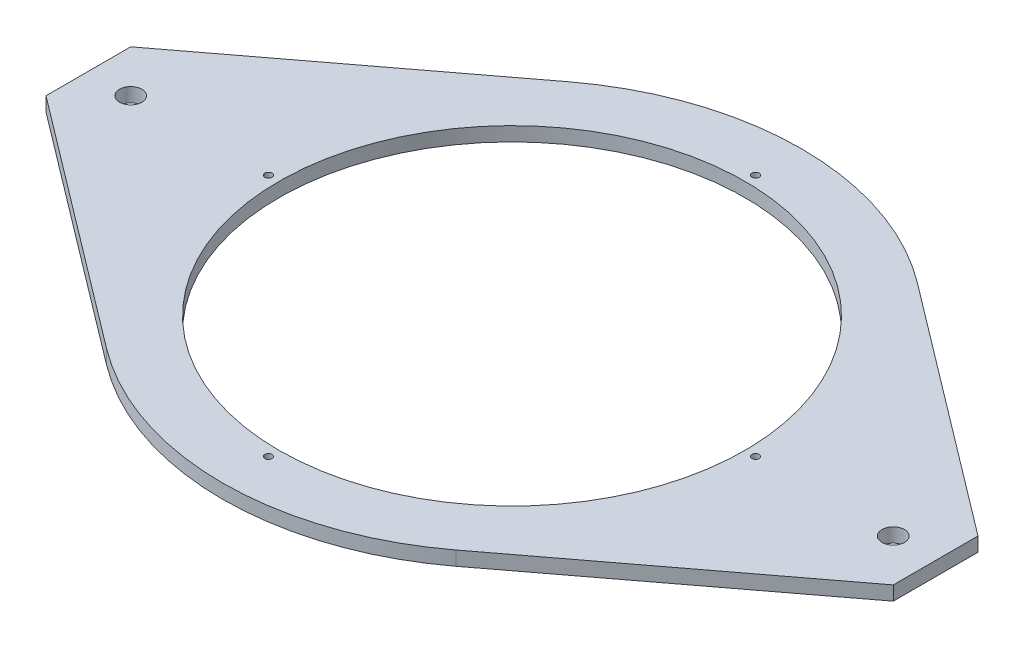
SolidWorks part; units mm, degrees
material "6061-T6 (SS)"
ref_plane "Front Plane" through (0, 0, 0) normal (0, 0, 1) x (1, 0, 0)
ref_plane "Top Plane" through (0, 0, 0) normal (0, 1, 0) x (1, 0, 0)
ref_plane "Right Plane" through (0, 0, 0) normal (1, 0, 0) x (0, 0, -1)
sketch "Sketch1" plane through (0, 0, 0) normal (0, 1, 0) x (1, 0, 0)
  line L2 (-190.5, 19.05) -> (-190.5, -19.05)
  line L4 (190.5, 19.05) -> (190.5, -19.05)
  line L5 (-190.5, 19.05) -> (190.5, -19.05) construction
  line L6 (-190.5, -19.05) -> (190.5, 19.05) construction
  line L8 (-190.5, 19.05) -> (-78.5743, 103.7864)
  line L9 (-190.5, -19.05) -> (-78.5743, -103.7864)
  line L10 (190.5, 19.05) -> (78.5743, 103.7864)
  line L11 (190.5, -19.05) -> (78.5743, -103.7864)
  circle A0 centre (0, 0) radius 104.775
  arc A1 (-78.5743, -103.7864) -> (78.5743, -103.7864) centre (0, 0) ccw
  arc A2 (78.5743, 103.7864) -> (-78.5743, 103.7864) centre (0, 0) ccw
  point P0 (0, 0)
  dimension "D3" = 209.55
  dimension "D4" = 25.4
  dimension "D1" = 381
  dimension "D2" = 38.1
extrude "Boss-Extrude1" add sketch "Sketch1" along normal blind 6.35
hole_wizard "#4 Clearance Hole1" positions "Sketch2" profile "Sketch3" hole size "#4" standard "ANSI Inch" end condition through all
sketch "Sketch2" plane through (0, 6.35, 0) normal (0, 1, 0) x (1, 0, 0)
  circle A0 centre (0, 0) radius 109.5375
  circle A1 centre (0, 0) radius 104.775 construction
  point P7 (0, 109.5375)
  point P9 (109.5375, 0)
  point P11 (0, -109.5375)
  point P13 (-109.5375, 0)
  dimension "D1" = 4.7625
sketch "Sketch3" plane through (0, 6.35, -109.5375) normal (1, 0, 0) x (0, 0, 1)
  line L0 (0, 0) -> (0, 6.35)
  line L1 (0, 6.35) -> (1.6319, 6.35)
  line L2 (1.6319, 6.35) -> (1.6319, 0)
  line L5 (1.6319, 0) -> (0, 0)
  line L11 (0, -6.35) -> (0, 107.95) construction
  dimension "Thru Hole Dia." = 3.2639
  dimension "Thru Hole Depth" = 6.35
hole_wizard "3/8 Clearance Hole1" positions "Sketch4" profile "Sketch5" hole size "3/8" standard "ANSI Inch" end condition through all
sketch "Sketch4" plane through (0, 6.35, 0) normal (0, 1, 0) x (1, 0, 0)
  line L0 (-171.45, 0) -> (171.45, 0) construction
  point P0 (-171.45, 0)
  point P2 (171.45, 0)
  dimension "D1" = 342.9
sketch "Sketch5" plane through (-171.45, 6.35, 0) normal (1, 0, 0) x (0, 0, 1)
  line L0 (0, 0) -> (0, 6.35)
  line L1 (0, 6.35) -> (5.0419, 6.35)
  line L2 (5.0419, 6.35) -> (5.0419, 0)
  line L5 (5.0419, 0) -> (0, 0)
  line L11 (0, -6.35) -> (0, 107.95) construction
  dimension "Thru Hole Dia." = 10.0838
  dimension "Thru Hole Depth" = 6.35
